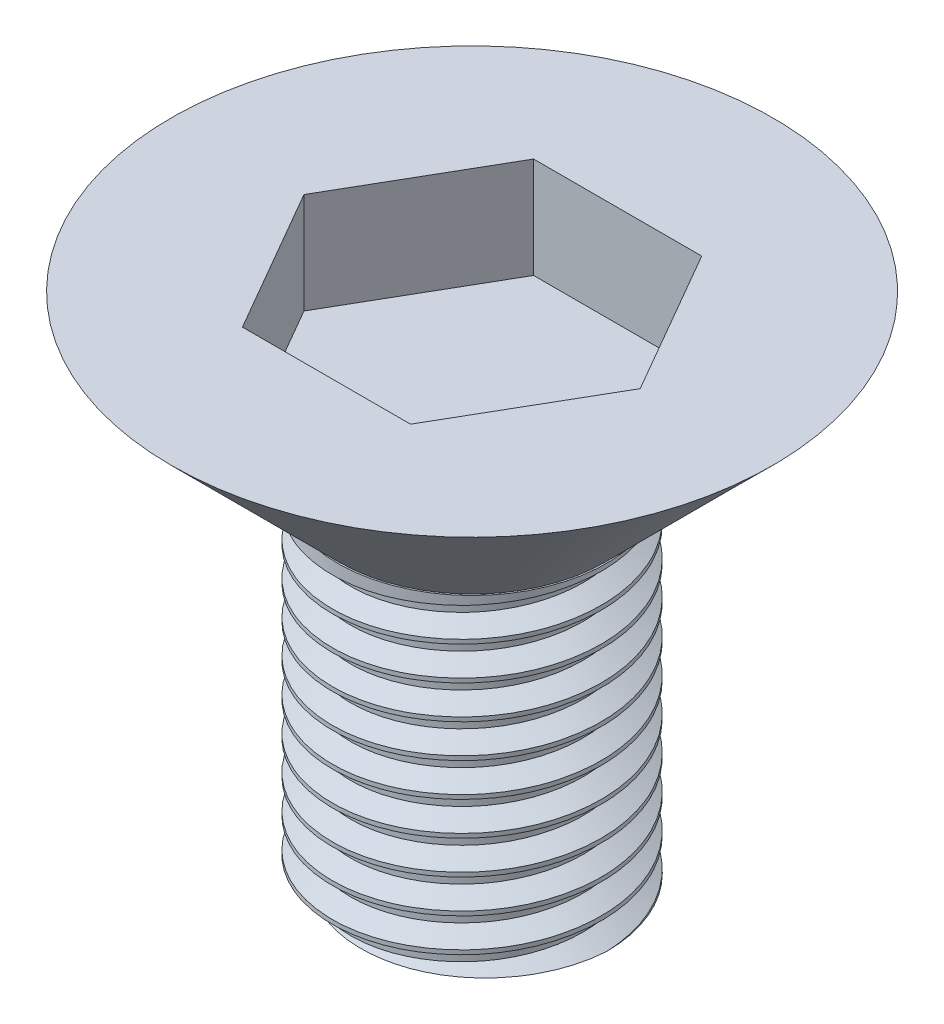
SolidWorks part; units mm, degrees
ref_plane "Alzado" through (0, 0, 0) normal (0, 0, 1) x (1, 0, 0)
ref_plane "Planta" through (0, 0, 0) normal (0, 1, 0) x (1, 0, 0)
ref_plane "Vista lateral" through (0, 0, 0) normal (1, 0, 0) x (0, 0, -1)
sketch "Croquis1" plane through (0, 0, 0) normal (0, 1, 0) x (1, 0, 0)
  circle A0 centre (0, 0) radius 8.95
  dimension "D1" = 17.9
extrude "Saliente-Extruir1" add sketch "Croquis1" against normal blind 5 draft 45
sketch "Croquis2" plane through (0, -5, 0) normal (0, -1, 0) x (1, 0, 0)
  circle A0 centre (0, 0) radius 4
  dimension "D1" = 8
extrude "Saliente-Extruir2" add sketch "Croquis2" along normal blind 10
thread "Rosca1" pitch 1 method cut profile "Perfil de rosca1" start angle 0, offset 1, length 10.5, pitch 1, diameter 8
ref_plane "Plano1" through (4, -16, 0) normal (0, 0, 1) x (1, 0, 0)
sketch "Perfil de rosca1" plane through (4, -16, 0) normal (0, 0, 1) x (1, 0, 0)
  line L0 (0, 0) -> (0, 1) construction
  line L11 (0, 0) -> (0, 0.875)
  line L12 (0, 0.875) -> (-0.5413, 0.5625)
  line L13 (-0.5413, 0.5625) -> (-0.5413, 0.3125)
  line L15 (-0.5413, 0.3125) -> (0, 0)
  line L17 (-0.5413, 0.4375) -> (0, 0.4375) construction
  point P2 (0, 0)
  dimension "Pitch" = 1
  dimension "Profile_Angle" = 60
  dimension "Profile_Land" = 0.25
  dimension "Profile_Height" = 0.5413
sketch "Croquis5" plane through (0, 0, 0) normal (0, 1, 0) x (1, 0, 0)
  line L1 (5, 0) -> (2.5, 4.3301)
  line L2 (2.5, 4.3301) -> (-2.5, 4.3301)
  line L3 (-2.5, 4.3301) -> (-5, 0)
  line L4 (-5, 0) -> (-2.5, -4.3301)
  line L5 (-2.5, -4.3301) -> (2.5, -4.3301)
  line L6 (2.5, -4.3301) -> (5, 0)
  circle A0 centre (0, 0) radius 4.3301 construction
  dimension "D1" = 5
extrude "Cortar-Extruir1" cut sketch "Croquis5" against normal blind 3
